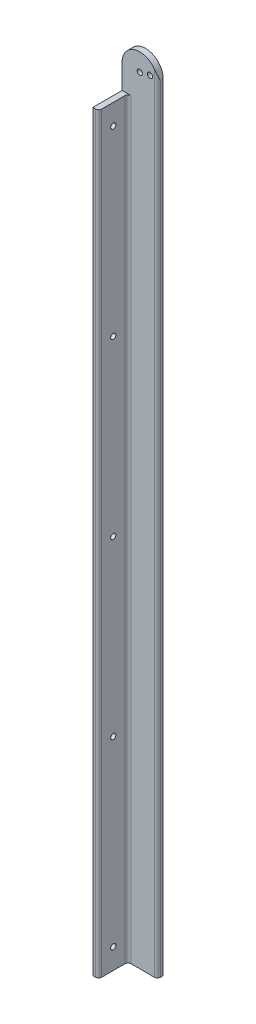
SolidWorks part; units mm, degrees
material "6061 Alloy"
ref_plane "Front Plane" through (0, 0, 0) normal (0, 0, 1) x (1, 0, 0)
ref_plane "Top Plane" through (0, 0, 0) normal (0, 1, 0) x (1, 0, 0)
ref_plane "Right Plane" through (0, 0, 0) normal (1, 0, 0) x (0, 0, -1)
sketch "Sketch2" plane through (0, 0, 0) normal (0, 1, 0) x (1, 0, 0)
  line L0 (0, 0) -> (19.05, 0)
  line L1 (0, 0) -> (0, 19.05)
  line L2 (4.7625, 3.175) -> (17.4625, 3.175)
  line L3 (3.175, 4.7625) -> (3.175, 17.4625)
  line L4 (0, 19.05) -> (1.5875, 19.05)
  line L5 (19.05, 1.5875) -> (19.05, 0)
  line L6 (3.175, 3.175) -> (3.175, 19.05) construction
  line L7 (3.175, 3.175) -> (19.05, 3.175) construction
  arc A0 (3.175, 17.4625) -> (1.5875, 19.05) centre (1.5875, 17.4625) ccw
  arc A1 (3.175, 4.7625) -> (4.7625, 3.175) centre (4.7625, 4.7625) ccw
  arc A2 (17.4625, 3.175) -> (19.05, 1.5875) centre (17.4625, 1.5875) cw
  dimension "D2" = 1.5875
  dimension "D1" = 3.175
extrude "Boss-Extrude1" add sketch "Sketch2" along normal blind 431.8
sketch "Sketch4" plane through (3.175, 0, 0) normal (1, 0, 0) x (0, 0, -1)
  line L0 (19.05, 431.8) -> (19.05, 406.4)
  line L1 (19.05, 431.8) -> (19.05, 0) construction
  line L2 (19.05, 406.4) -> (3.175, 406.4)
  line L3 (3.175, 431.8) -> (3.175, 0) construction
  line L4 (3.175, 406.4) -> (3.175, 431.8)
  line L5 (3.175, 431.8) -> (19.05, 431.8)
extrude "Cut-Extrude1" cut sketch "Sketch4" against normal blind 6.35
sketch "Sketch5" plane through (3.175, 0, 0) normal (-1, 0, 0) x (0, 0, 1)
  line L8 (-4.7625, 406.4) -> (-3.175, 406.4)
  line L9 (-3.175, 406.4) -> (-3.175, 431.8)
  line L10 (-3.175, 431.8) -> (-4.7625, 431.8)
  line L11 (-4.7625, 431.8) -> (-4.7625, 406.4)
  line L12 (-4.7625, 406.4) -> (-3.175, 406.4)
  line L13 (-3.175, 406.4) -> (-3.175, 431.8)
  line L14 (-3.175, 431.8) -> (-4.7625, 431.8)
  line L15 (-4.7625, 431.8) -> (-4.7625, 406.4)
  dimension "D1" = 0
extrude "Cut-Extrude2" cut sketch "Sketch5" against normal blind 6.35
sketch "Sketch6" plane through (3.175, 0, 0) normal (1, 0, 0) x (0, 0, -1)
  line L0 (19.05, 0) -> (3.175, 0) construction
  line L1 (11.1125, 0) -> (11.1125, 15.875) construction
  line L2 (19.05, 406.4) -> (3.175, 406.4) construction
  line L3 (11.1125, 406.4) -> (11.1125, 390.525) construction
  line L4 (11.1125, 15.875) -> (11.1125, 203.2) construction
  line L5 (11.1125, 203.2) -> (11.1125, 390.525) construction
  circle A1 centre (11.1125, 109.5375) radius 1.4224
  circle A2 centre (11.1125, 203.2) radius 1.4224
  circle A3 centre (11.1125, 296.8625) radius 1.4224
  circle A5 centre (11.1125, 11.1125) radius 1.4224
  circle A6 centre (11.1125, 395.2875) radius 1.4224
  point P12 (11.1125, 203.2)
  point P13 (11.1125, 296.8625)
  point P15 (11.1125, 109.5375)
  dimension "D2" = 2.8448
  dimension "D3" = 2.8448
  dimension "D4" = 2.8448
  dimension "D6" = 2.8448
  dimension "D7" = 2.8448
extrude "Cut-Extrude3" cut sketch "Sketch6" against normal blind 5.08
sketch "Sketch7" plane through (0, 431.8, 0) normal (0, 1, 0) x (1, 0, 0)
  line L8 (17.4625, 3.175) -> (0, 3.175)
  line L9 (0, 3.175) -> (0, 0)
  line L10 (0, 0) -> (19.05, 0)
  line L11 (19.05, 0) -> (19.05, 1.5875)
  line L12 (17.4625, 3.175) -> (0, 3.175)
  line L13 (0, 3.175) -> (0, 0)
  line L14 (0, 0) -> (19.05, 0)
  line L15 (19.05, 0) -> (19.05, 1.5875)
  arc A2 (19.05, 1.5875) -> (17.4625, 3.175) centre (17.4625, 1.5875) ccw
  arc A3 (19.05, 1.5875) -> (17.4625, 3.175) centre (17.4625, 1.5875) ccw
  dimension "D1" = 0
extrude "Cut-Extrude4" cut sketch "Sketch7" against normal blind 2.54
sketch "Sketch8" plane through (0, 0, -3.175) normal (0, 0, -1) x (-1, 0, 0)
  line L0 (0, 429.26) -> (0, 419.735) construction
  line L1 (0, 429.26) -> (0, 406.4) construction
  line L2 (0, 419.735) -> (-9.525, 419.735) construction
  line L3 (-9.525, 419.735) -> (-9.525, 431.0069) construction
  line L4 (-9.525, 419.735) -> (-15.0935, 421.0206) construction
  circle A0 centre (-9.525, 419.735) radius 1.4224
  circle A1 centre (-15.0935, 421.0206) radius 1.4224
  dimension "D1" = 2.8448
  dimension "D2" = 2.8448
  dimension "D3" = 77
extrude "Cut-Extrude5" cut sketch "Sketch8" against normal blind 5.08
ref_plane "Plane1" through (0, 0, 2.54) normal (0, 0, 1) x (1, 0, 0)
mirror "Mirror3" about plane through (0, 0, 2.54) normal (0, 0, 1) of bodies 106
sketch "Sketch9" plane through (0, 0, 2.54) normal (0, 0, 1) x (1, 0, 0)
  line L1 (-6.6248, 469.5409) -> (22.2362, 469.5409)
  line L2 (-6.6248, 469.5409) -> (-6.6248, -77.9837)
  line L3 (-6.6248, -77.9837) -> (22.2362, -77.9837)
  line L4 (22.2362, 469.5409) -> (22.2362, -77.9837)
extrude "Cut-Extrude6" cut sketch "Sketch9" against normal blind 30.48
sketch "Sketch10" plane through (0, 0, 8.255) normal (0, 0, 1) x (1, 0, 0)
  line L0 (9.525, 419.735) -> (9.525, 415.925) construction
  line L6 (9.525, 419.735) -> (0, 429.26) construction
  line L9 (19.05, 419.735) -> (19.05, 429.26)
  line L10 (19.05, 429.26) -> (0, 429.26)
  line L11 (0, 419.735) -> (0, 429.26)
  line L13 (19.05, 429.26) -> (9.525, 419.735) construction
  arc A3 (19.05, 419.735) -> (0, 419.735) centre (9.525, 419.735) ccw
  line M4 (17.4625, 429.26) -> (0, 429.26)
  line M5 (0, 429.26) -> (0, 406.4)
  line M9 (17.4625, 0) -> (17.4625, 429.26)
extrude "Cut-Extrude7" cut sketch "Sketch10" against normal blind 5.08 contours M9 | M9 M4 | M5 region at (18.3487, 426.1569, 8.255) region at (2.1276, 427.1324, 8.255) region at (15.5776, 428.0522, 8.255)
